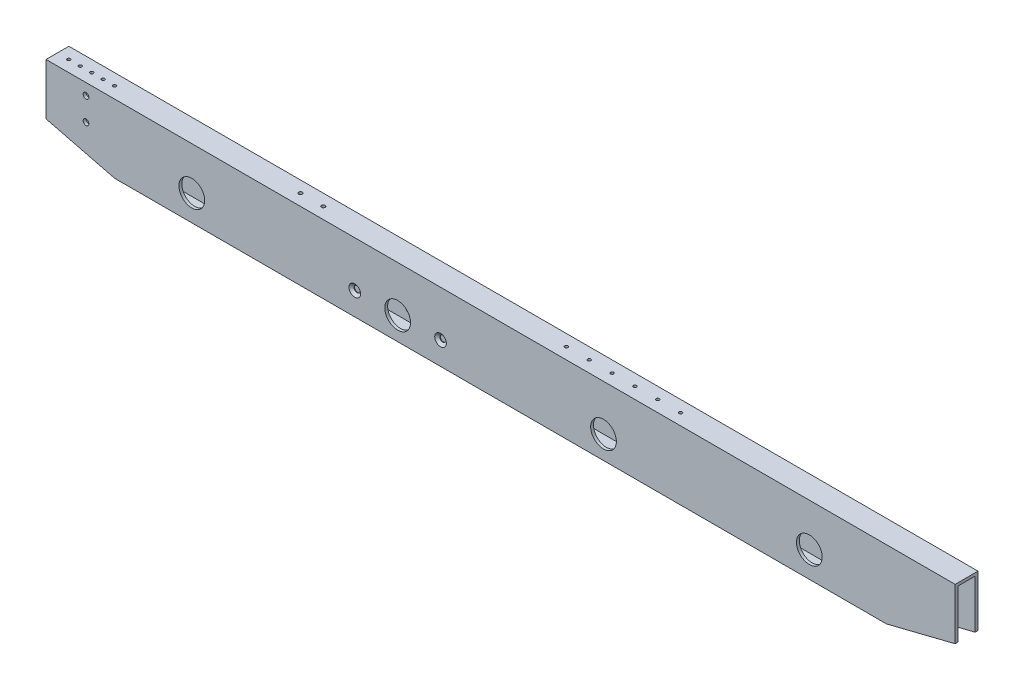
SolidWorks part; units mm, degrees
material "6061-T6 (SS)"
ref_plane "Front Plane" through (0, 0, 0) normal (0, 0, 1) x (1, 0, 0)
ref_plane "Top Plane" through (0, 0, 0) normal (0, 1, 0) x (1, 0, 0)
ref_plane "Right Plane" through (0, 0, 0) normal (1, 0, 0) x (0, 0, -1)
sketch "Sketch1" plane through (0, 0, 0) normal (0, 0, 1) x (1, 0, 0)
  line L0 (0, -12.7) -> (-342.9, -9.525) construction
  line L1 (-504.825, 38.1) -> (504.825, 38.1)
  line L2 (-504.825, 38.1) -> (-504.825, -38.1)
  line L3 (-504.825, -38.1) -> (504.825, -38.1)
  line L4 (504.825, 38.1) -> (504.825, -38.1)
  line L5 (-504.825, 38.1) -> (504.825, -38.1) construction
  line L6 (-504.825, -38.1) -> (504.825, 38.1) construction
  line L7 (-504.825, -38.1) -> (504.825, -38.1) construction
  line L8 (-504.825, -38.1) -> (-504.825, -12.7) construction
  line L9 (-327.025, -63.5) -> (327.025, -63.5) construction
  line L10 (-504.825, -12.7) -> (504.825, -12.7) construction
  line L11 (504.825, -38.1) -> (504.825, -12.7) construction
  line L12 (0, -12.7) -> (342.9, -9.525) construction
  line L13 (-114.3, -12.7) -> (114.3, -12.7) construction
  circle A0 centre (114.3, -12.7) radius 14.2875
  circle A1 centre (-342.9, -9.525) radius 14.2875
  circle A2 centre (342.9, -9.525) radius 14.2875
  circle A3 centre (-114.3, -12.7) radius 14.2875
  point P0 (0, 0)
  dimension "D5" = 28.575
  dimension "D4" = 28.575
  dimension "D8" = 228.6
  dimension "D6" = 228.6
  dimension "D7" = 228.6
  dimension "D1" = 76.2
  dimension "D2" = 1009.65
  dimension "D3" = 25.4
extrude "Boss-Extrude2" add sketch "Sketch1" along normal mid plane 25.4
sketch "Sketch3" plane through (504.825, 0, 0) normal (1, 0, 0) x (0, 0, -1)
  line L8 (9.525, -34.925) -> (9.525, 34.925)
  line L9 (9.525, 34.925) -> (-9.525, 34.925)
  line L10 (-9.525, 34.925) -> (-9.525, -34.925)
  line L11 (-9.525, -34.925) -> (9.525, -34.925)
  line L12 (9.525, -34.925) -> (9.525, 34.925)
  line L13 (9.525, 34.925) -> (-9.525, 34.925)
  line L14 (-9.525, 34.925) -> (-9.525, -34.925)
  line L15 (-9.525, -34.925) -> (9.525, -34.925)
  dimension "D1" = 3.175
extrude "Cut-Extrude2" cut sketch "Sketch3" against normal through all
sketch "Sketch4" plane through (0, 0, 12.7) normal (0, 0, 1) x (1, 0, 0)
  line L0 (-504.825, -38.1) -> (-504.825, -19.05)
  line L1 (-504.825, 38.1) -> (-504.825, -38.1) construction
  line L2 (-504.825, -19.05) -> (-428.625, -38.1)
  line L3 (-504.825, -38.1) -> (504.825, -38.1) construction
  line L4 (-428.625, -38.1) -> (-504.825, -38.1)
  line L5 (0, -38.1) -> (0, 38.1) construction
  line L6 (504.825, 38.1) -> (-504.825, 38.1) construction
  line L7 (428.625, -38.1) -> (504.825, -38.1)
  line L8 (504.825, -38.1) -> (504.825, -19.05)
  line L9 (504.825, -19.05) -> (428.625, -38.1)
  dimension "D1" = 19.05
  dimension "D2" = 76.2
  dimension "D3" = 57.15
extrude "Cut-Extrude3" cut sketch "Sketch4" against normal through all
sketch "Sketch9" plane through (0, 38.1, 0) normal (0, 1, 0) x (1, 0, 0)
  line L0 (-504.825, -12.7) -> (-504.825, 12.7) construction
  line L1 (0, -12.7) -> (0, 12.7) construction
  line L2 (504.825, -12.7) -> (-504.825, -12.7) construction
  line L3 (504.825, 12.7) -> (-504.825, 12.7) construction
  circle A0 centre (-492.125, 0) radius 1.7272
  circle A1 centre (-441.325, 0) radius 1.7272
  circle A2 centre (-479.425, 0) radius 1.7272
  circle A3 centre (-466.725, 0) radius 1.7272
  circle A4 centre (-454.025, 0) radius 1.7272
  point P2 (-504.825, 0)
  dimension "D1" = 3.4544
  dimension "D2" = 12.7
  dimension "D3" = 4
  dimension "D4" = 2
extrude "Cut-Extrude5" cut sketch "Sketch9" against normal blind 6.35
sketch "Sketch12" plane through (0, 38.1, 0) normal (0, 1, 0) x (1, 0, 0)
  line L0 (504.825, -12.7) -> (504.825, 12.7) construction
  circle A0 centre (187.325, 0) radius 1.7272
  circle A1 centre (161.925, 0) radius 1.7272
  circle A2 centre (136.525, 0) radius 1.7272
  circle A3 centre (111.125, 0) radius 1.7272
  circle A4 centre (85.725, 0) radius 1.7272
  circle A5 centre (60.325, 0) radius 1.7272
  point P2 (504.825, 0)
  dimension "D1" = 3.4544
  dimension "D2" = 317.5
  dimension "D3" = 6
extrude "Cut-Extrude8" cut sketch "Sketch12" against normal blind 5.08
hole_wizard "CSK for 1/4 Flat Head Machine Screw (100)1" positions "Sketch14" profile "Sketch13" countersink size "1/4" standard "ANSI Inch" end condition through all
sketch "Sketch14" plane through (0, 0, 12.7) normal (0, 0, 1) x (1, 0, 0)
  circle A1 centre (-114.3, -12.7) radius 14.2875 construction
  point P0 (-66.675, -12.7)
  point P2 (-161.925, -12.7)
  dimension "D4" = 47.625
  dimension "D3" = 47.625
sketch "Sketch13" plane through (-66.675, -12.7, 12.7) normal (1, 0, 0) x (0, -1, 0)
  line L0 (0, 0) -> (0, 25.4)
  line L1 (0, 25.4) -> (3.3782, 25.4)
  line L2 (3.3782, 25.4) -> (3.3782, 2.5682)
  line L3 (3.3782, 2.5682) -> (6.4389, 0)
  line L5 (6.4389, 0) -> (0, 0)
  line L6 (-3.3782, 2.5682) -> (-6.4389, 0) construction
  line L11 (0, -6.35) -> (0, 107.95) construction
  dimension "Thru Hole Dia." = 6.7564
  dimension "Thru Hole Depth" = 25.4
  dimension "Near C'Sink Dia." = 12.8778
  dimension "Near C'Sink Angle" = 100
sketch "Sketch15" plane through (0, -38.1, 0) normal (0, -1, 0) x (-1, 0, 0)
  line L1 (-504.825, 9.525) -> (-504.825, -9.525) construction
  circle A0 centre (396.875, 0) radius 1.7272
  circle A1 centre (320.675, 0) radius 1.7272
  circle A2 centre (244.475, 0) radius 1.7272
  circle A3 centre (168.275, 0) radius 1.7272
  circle A4 centre (92.075, 0) radius 1.7272
  circle A5 centre (15.875, 0) radius 1.7272
  circle A6 centre (-60.325, 0) radius 1.7272
  dimension "D1" = 3.4544
  dimension "D2" = 444.5
  dimension "D3" = 7
extrude "Cut-Extrude9" cut sketch "Sketch15" against normal blind 6.35
sketch "Sketch16" plane through (0, 0, -12.7) normal (0, 0, -1) x (-1, 0, 0)
  circle A0 centre (114.3, -12.7) radius 17.4625
  dimension "D1" = 34.925
extrude "Cut-Extrude10" cut sketch "Sketch16" against normal blind 3.81
hole_wizard "1/4 (0.25) Diameter Hole1" positions "Sketch19" profile "Sketch18" hole size "1/4" standard "ANSI Inch" end condition through all
sketch "Sketch19" plane through (0, 0, 12.7) normal (0, 0, 1) x (1, 0, 0)
  line L0 (-504.825, 38.1) -> (-504.825, -19.05) construction
  line L1 (-479.425, -25.4) -> (-479.425, 3.7361) construction
  line L2 (-428.625, -38.1) -> (-504.825, -19.05) construction
  line L5 (504.825, 38.1) -> (-504.825, 38.1) construction
  point P0 (-460.375, 25.4)
  point P2 (-460.375, 0)
  dimension "D1" = 19.05
  dimension "D2" = 25.4
  dimension "D3" = 25.4
  dimension "D4" = 12.7
sketch "Sketch18" plane through (-460.375, 25.4, 12.7) normal (1, 0, 0) x (0, -1, 0)
  line L0 (0, 0) -> (0, 25.4)
  line L1 (0, 25.4) -> (3.175, 25.4)
  line L2 (3.175, 25.4) -> (3.175, 0)
  line L5 (3.175, 0) -> (0, 0)
  line L11 (0, -6.35) -> (0, 107.95) construction
  dimension "Thru Hole Dia." = 6.35
  dimension "Thru Hole Depth" = 25.4
hole_wizard "#10-32 Tapped Hole3" positions "Sketch23" profile "Sketch22" tap size "#10-32" standard "ANSI Inch" end condition through all
sketch "Sketch23" plane through (0, 38.1, 0) normal (0, 1, 0) x (1, 0, 0)
  line L0 (-504.825, -12.7) -> (-504.825, 12.7) construction
  point P0 (-234.95, 0)
  point P4 (-209.55, 0)
  dimension "D1" = 269.875
  dimension "D2" = 25.4
sketch "Sketch22" plane through (-234.95, 38.1, 0) normal (1, 0, 0) x (0, 0, 1)
  line L0 (0, 0) -> (0, 76.2)
  line L1 (0, 76.2) -> (2.0193, 76.2)
  line L2 (2.0193, 76.2) -> (2.0193, 0)
  line L5 (2.0193, 0) -> (0, 0)
  line L11 (0, -6.35) -> (0, 107.95) construction
  dimension "Thread Major Dia." = 4.0386
  dimension "Thru Tap Drill Depth" = 76.2
